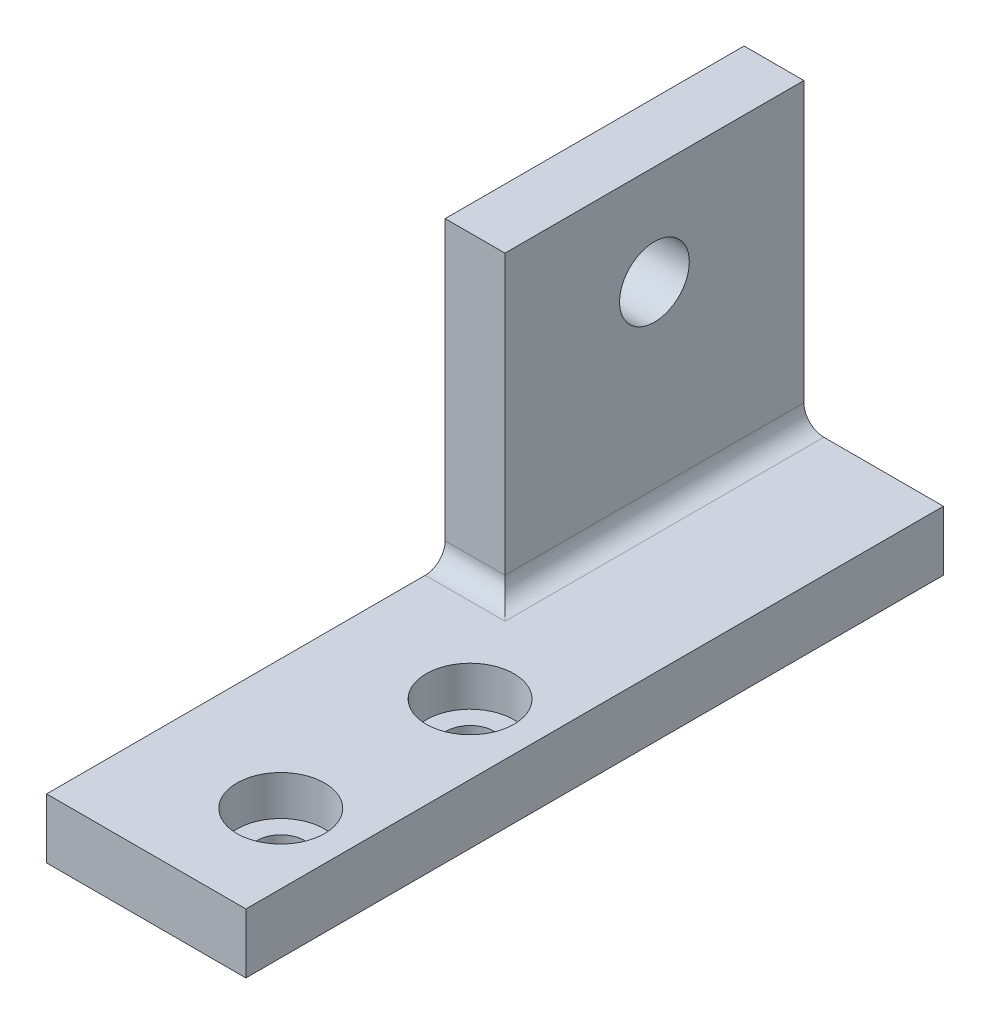
SolidWorks part; units mm, degrees
ref_plane "Front Plane" through (0, 0, 0) normal (0, 0, 1) x (1, 0, 0)
ref_plane "Top Plane" through (0, 0, 0) normal (0, 1, 0) x (1, 0, 0)
ref_plane "Right Plane" through (0, 0, 0) normal (1, 0, 0) x (0, 0, -1)
sketch "Sketch1" plane through (0, 0, 0) normal (0, 1, 0) x (1, 0, 0)
  line L0 (6.5, 5.25) -> (6.5, 14.75) construction
  line L1 (0, 0) -> (10, 0)
  line L2 (0, 0) -> (0, 20)
  line L3 (0, 20) -> (10, 20)
  line L4 (10, 0) -> (10, 20)
  circle A0 centre (6.5, 5.25) radius 1.175
  circle A1 centre (6.5, 14.75) radius 1.175
  point P9 (6.5, 10)
  point P10 (10, 10)
  dimension "D3" = 9.5
  dimension "D4" = 2.35
  dimension "D5" = 2.35
  dimension "D6" = 6.5
  dimension "D1" = 20
  dimension "D2" = 10
extrude "Boss-Extrude1" add sketch "Sketch1" along normal blind 3
sketch "Sketch2" plane through (0, 3, 0) normal (0, 1, 0) x (1, 0, 0)
  point P0 (6.5, 14.75)
  point P1 (6.5, 5.25)
hole_wizard "CBORE for M2 SHCS1" positions "Sketch2" profile "Sketch3" counterbore size "M2" standard "ANSI Metric" end condition through all
sketch "Sketch3" plane through (6.5, 3, -14.75) normal (1, 0, 0) x (0, 0, 1)
  line L0 (0, 0) -> (0, 3)
  line L1 (0, 3) -> (1.2, 3)
  line L3 (1.2, 3) -> (1.2, 2)
  line L4 (1.2, 2) -> (2.2, 2)
  line L5 (2.2, 2) -> (2.2, 0)
  line L7 (2.2, 0) -> (0, 0)
  line L11 (0, -6.35) -> (0, 107.95) construction
  dimension "Thru Hole Dia." = 2.4
  dimension "Thru Hole Depth" = 3
  dimension "C'Bore Dia." = 4.4
  dimension "C'Bore Depth" = 2
sketch "Sketch6" plane through (0, 0, -20) normal (0, 0, -1) x (-1, 0, 0)
  line L1 (0, 0) -> (-10, 0)
  line L2 (0, 0) -> (0, 3)
  line L3 (0, 3) -> (-10, 3)
  line L4 (-10, 0) -> (-10, 3)
  line L5 (-10, 3) -> (0, 3) construction
  line L6 (-10, 3) -> (-10, 0) construction
  dimension "D1" = 0
extrude "Boss-Extrude2" add sketch "Sketch6" along normal blind 15
sketch "Sketch8" plane through (0, 3, 0) normal (0, 1, 0) x (1, 0, 0)
  line L2 (0, 35) -> (3, 35)
  line L3 (0, 35) -> (0, 20)
  line L4 (0, 20) -> (3, 20)
  line L5 (3, 35) -> (3, 20)
  dimension "D1" = 3
extrude "Boss-Extrude3" add sketch "Sketch8" along normal blind 15
sketch "Sketch9" plane through (3, 0, 0) normal (1, 0, 0) x (0, 0, -1)
  line L0 (20, 18) -> (35, 18) construction
  line L1 (0, 3) -> (35, 3) construction
  circle A0 centre (27.5, 13) radius 1.75
  point P5 (27.5, 18)
  dimension "D1" = 10
extrude "Cut-Extrude1" cut sketch "Sketch9" against normal through all
fillet "Fillet1" radius 1 2 edges at (1.5, 3, -20) (3, 3, -27.5)
